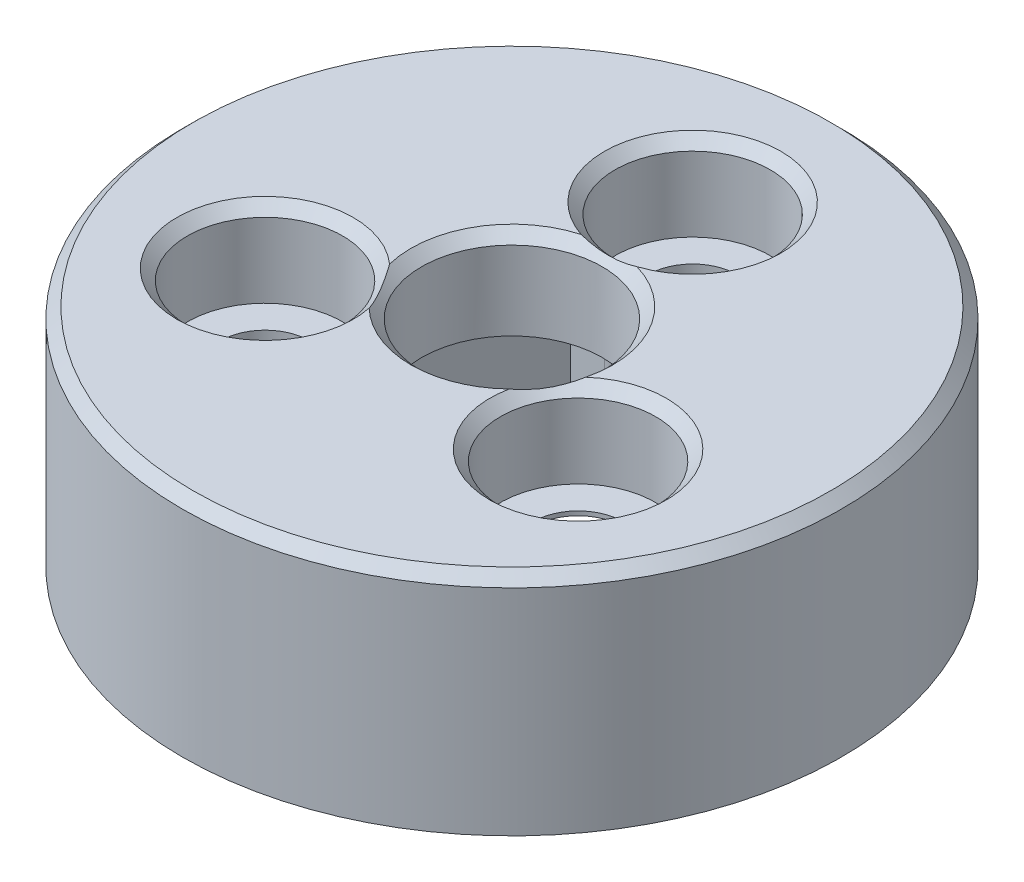
SolidWorks part; units mm, degrees
ref_plane "Front Plane" through (0, 0, 0) normal (0, 0, 1) x (1, 0, 0)
ref_plane "Top Plane" through (0, 0, 0) normal (0, 1, 0) x (1, 0, 0)
ref_plane "Right Plane" through (0, 0, 0) normal (1, 0, 0) x (0, 0, -1)
sketch "Sketch1" plane through (0, 0, 0) normal (0, 1, 0) x (1, 0, 0)
  circle A0 centre (0, 0) radius 15.5
  dimension "D1" = 31
extrude "Boss-Extrude1" add sketch "Sketch1" along normal blind 10.6
sketch "Sketch2" plane through (0, 10.6, 0) normal (0, 1, 0) x (1, 0, 0)
  circle A0 centre (0, 0) radius 8.5 construction
  circle A1 centre (0, 8.5) radius 2.1
  circle A2 centre (7.3612, -4.25) radius 2.1
  circle A3 centre (-7.3612, -4.25) radius 2.1
  point P12 (0, 0)
  dimension "D1" = 17
  dimension "D3" = 4.2
  dimension "D2" = 3
extrude "Cut-Extrude1" cut sketch "Sketch2" against normal through all
sketch "Sketch3" plane through (0, 10.6, 0) normal (0, 1, 0) x (1, 0, 0)
  circle A0 centre (0, 0) radius 4.25
  dimension "D1" = 8.5
extrude "Cut-Extrude2" cut sketch "Sketch3" against normal through all
sketch "Sketch4" plane through (0, 0, 0) normal (0, -1, 0) x (1, 0, 0)
  line L1 (3.7409, -6.4401) -> (7.4478, 0.0197)
  line L2 (7.4478, 0.0197) -> (3.7069, 6.4598)
  line L3 (3.7069, 6.4598) -> (-3.7409, 6.4401)
  line L4 (-3.7409, 6.4401) -> (-7.4478, -0.0197)
  line L5 (-7.4478, -0.0197) -> (-3.7069, -6.4598)
  line L6 (-3.7069, -6.4598) -> (3.7409, -6.4401)
  circle A0 centre (0, 0) radius 6.45 construction
  dimension "D1" = 12.9
extrude "Cut-Extrude3" cut sketch "Sketch4" against normal blind 6.4
sketch "Sketch5" plane through (0, 10.6, 0) normal (0, 1, 0) x (1, 0, 0)
  circle A0 centre (0, 8.5) radius 3.65
  circle A1 centre (7.3612, -4.25) radius 3.65
  circle A2 centre (-7.3612, -4.25) radius 3.65
  dimension "D1" = 7.3
extrude "Cut-Extrude4" cut sketch "Sketch5" against normal blind 4
chamfer "Chamfer1" distance 0.5 angle 45 5 edges at (0, 10.6, 15.5) (-7.3612, 10.6, 7.9) (7.3612, 10.6, 7.9) (0, 10.6, 4.25) (0, 10.6, -4.85)
fillet "Скругление1" radius 0.5 6 edges at (5.8175, 3.2, 2.8263) (5.3597, 3.2, 3.6143) (-5.3564, 3.2, 3.6249) (-5.81, 3.2, 2.8345) (0.4502, 3.2, -6.4488) (-0.4611, 3.2, -6.4512)
